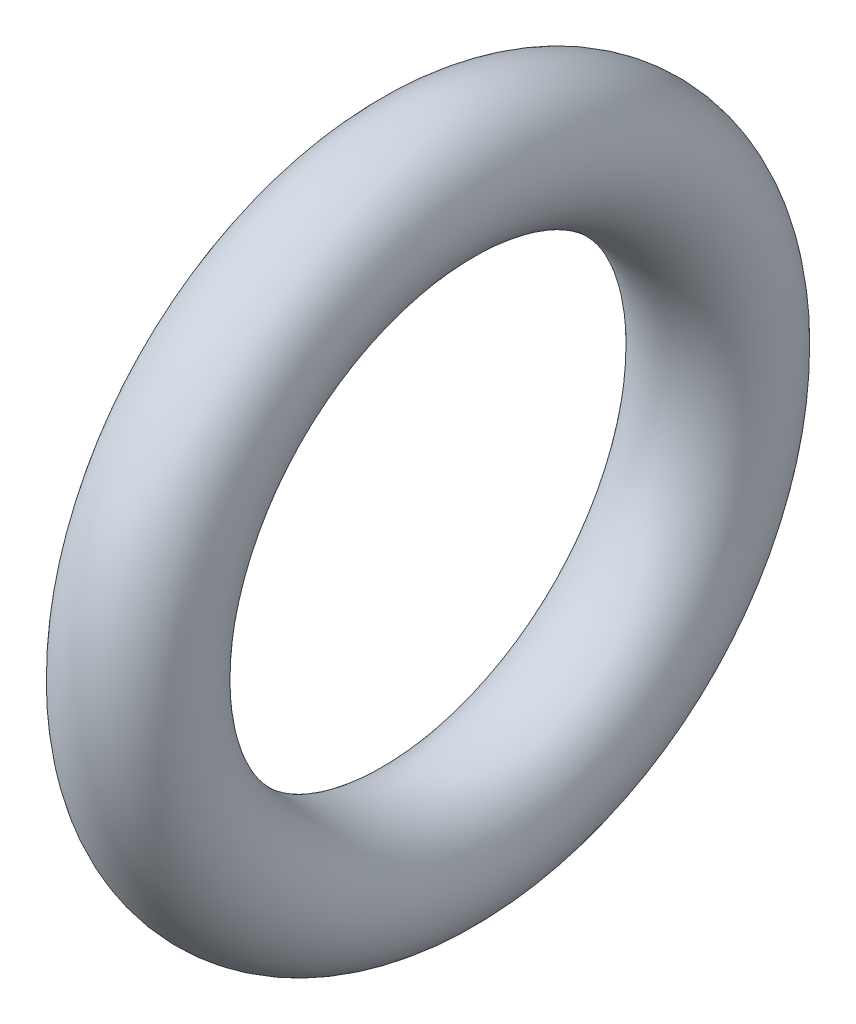
SolidWorks part; units mm, degrees
material "Gummi"
ref_plane "Ebene vorne" through (0, 0, 0) normal (0, 0, 1) x (1, 0, 0)
ref_plane "Ebene oben" through (0, 0, 0) normal (0, 1, 0) x (1, 0, 0)
ref_plane "Ebene rechts" through (0, 0, 0) normal (1, 0, 0) x (0, 0, -1)
ref_axis "Achse1" through (1.375, 0, 0) along (-1, 0, 0)
sketch "Skizze1" plane through (0, 0, 0) normal (0, 0, 1) x (1, 0, 0)
  line L0 (0, 5.8) -> (0, 0) construction
  line L7 (-5.5188, 0) -> (-49.9899, 0) construction
  circle A0 centre (0, 5.8) radius 1.3
  point P3 (0, 7.1)
  point P6 (0, 4.5)
  dimension "D2" = 2.6
  dimension "D1" = 9
revolve "Rotation1" add sketch "Skizze1" angle 360 about L7
